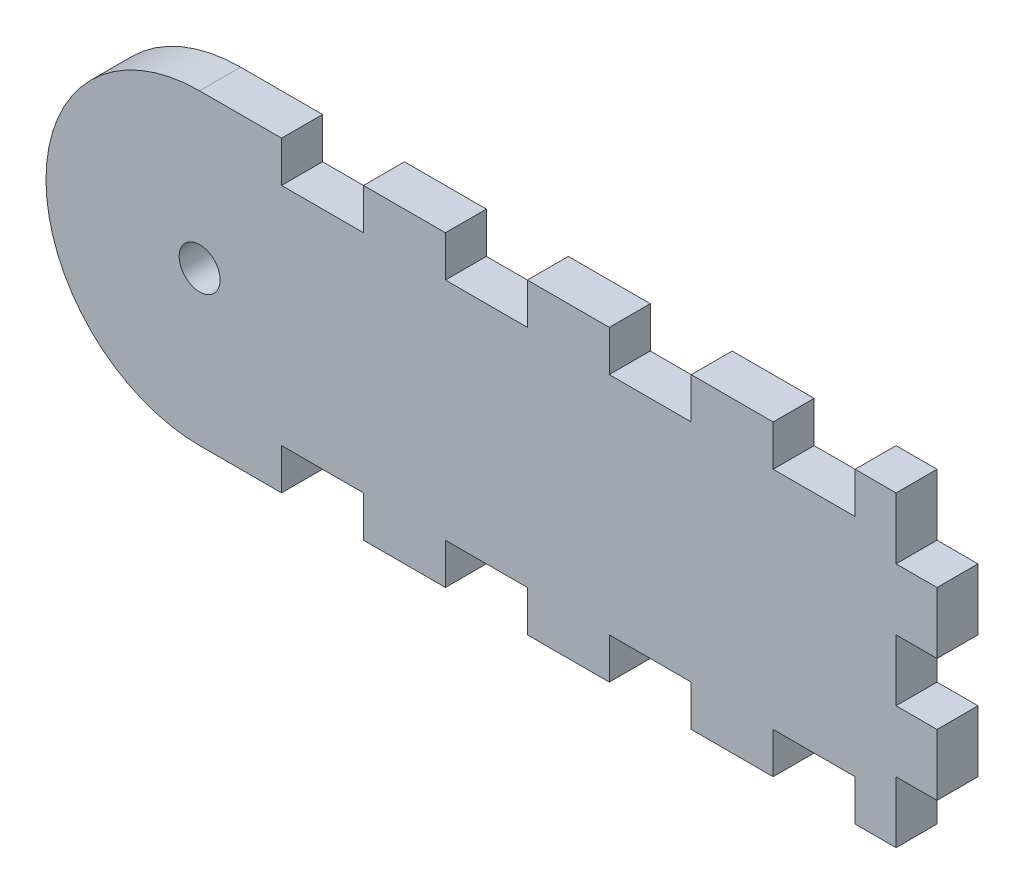
SolidWorks part; units mm, degrees
ref_plane "Front Plane" through (0, 0, 0) normal (0, 0, 1) x (1, 0, 0)
ref_plane "Top Plane" through (0, 0, 0) normal (0, 1, 0) x (1, 0, 0)
ref_plane "Right Plane" through (0, 0, 0) normal (1, 0, 0) x (0, 0, -1)
sketch "Sketch1" plane through (0, 0, 0) normal (0, 0, 1) x (1, 0, 0)
  line L1 (-57.15, -23.8125) -> (57.15, -23.8125)
  line L2 (-57.15, -23.8125) -> (-57.15, 23.8125) construction
  line L3 (-57.15, 23.8125) -> (57.15, 23.8125)
  line L4 (57.15, -23.8125) -> (57.15, 23.8125)
  line L5 (-57.15, -23.8125) -> (57.15, 23.8125) construction
  line L6 (-57.15, 23.8125) -> (57.15, -23.8125) construction
  arc A0 (-57.15, 23.8125) -> (-57.15, -23.8125) centre (-57.15, 0) ccw
  point P0 (0, 0)
  dimension "D1" = 47.625
  dimension "D2" = 114.3
extrude "Mass" add sketch "Sketch1" along normal blind 6.35
sketch "Sketch3" plane through (0, 0, 0) normal (0, 0, -1) x (-1, 0, 0)
  line L1 (-57.15, 23.8125) -> (57.15, 23.8125) construction
  line L2 (57.15, -23.8125) -> (-57.15, -23.8125) construction
  line L3 (-57.15, 23.8125) -> (-44.45, 23.8125) construction
  line L5 (-31.75, 17.4625) -> (-44.45, 17.4625)
  line L6 (-31.75, 17.4625) -> (-31.75, 30.1625)
  line L7 (-31.75, 30.1625) -> (-44.45, 30.1625)
  line L8 (-44.45, 17.4625) -> (-44.45, 30.1625)
  line L9 (-31.75, 17.4625) -> (-44.45, 30.1625) construction
  line L10 (-31.75, 30.1625) -> (-44.45, 17.4625) construction
  line L11 (-31.75, -30.1625) -> (-44.45, -30.1625)
  line L12 (-31.75, -30.1625) -> (-31.75, -17.4625)
  line L13 (-31.75, -17.4625) -> (-44.45, -17.4625)
  line L14 (-44.45, -30.1625) -> (-44.45, -17.4625)
  line L15 (-31.75, -30.1625) -> (-44.45, -17.4625) construction
  line L16 (-31.75, -17.4625) -> (-44.45, -30.1625) construction
  point P3 (-38.1, 23.8125)
  point P4 (-38.1, -23.8125)
  dimension "D1" = 12.7
  dimension "D2" = 12.7
  dimension "D3" = 12.7
sketch "Sketch4" plane through (0, 0, 0) normal (0, 0, -1) x (-1, 0, 0)
  circle A0 centre (57.15, 0) radius 3.175
  arc A1 (57.15, -23.8125) -> (57.15, 23.8125) centre (57.15, 0) ccw construction
  dimension "D1" = 6.35
extrude "Cut-Extrude1" cut sketch "Sketch4" against normal through all
extrude "Cut-Extrude2" cut sketch "Sketch3" against normal through all
pattern_linear "LPattern1" count 4 spacing 25.4 along (-1, 0, 0) of "Cut-Extrude2"
sketch "Sketch5" plane through (0, 0, 0) normal (0, 0, -1) x (-1, 0, 0)
  line L0 (-57.15, -23.8125) -> (-57.15, 23.8125) construction
  line L1 (-63.5, 4.7625) -> (-50.8, 4.7625)
  line L2 (-63.5, 4.7625) -> (-63.5, -4.7625)
  line L3 (-63.5, -4.7625) -> (-50.8, -4.7625)
  line L4 (-50.8, 4.7625) -> (-50.8, -4.7625)
  line L5 (-63.5, 4.7625) -> (-50.8, -4.7625) construction
  line L6 (-63.5, -4.7625) -> (-50.8, 4.7625) construction
  point P0 (-57.15, 0)
  dimension "D1" = 9.525
  dimension "D2" = 12.7
extrude "Cut-Extrude3" cut sketch "Sketch5" against normal through all
pattern_linear "LPattern2" count 2 spacing 19.05 along (0, -1, 0) count 2 spacing 19.05 along (0, 1, 0) of "Cut-Extrude3"
